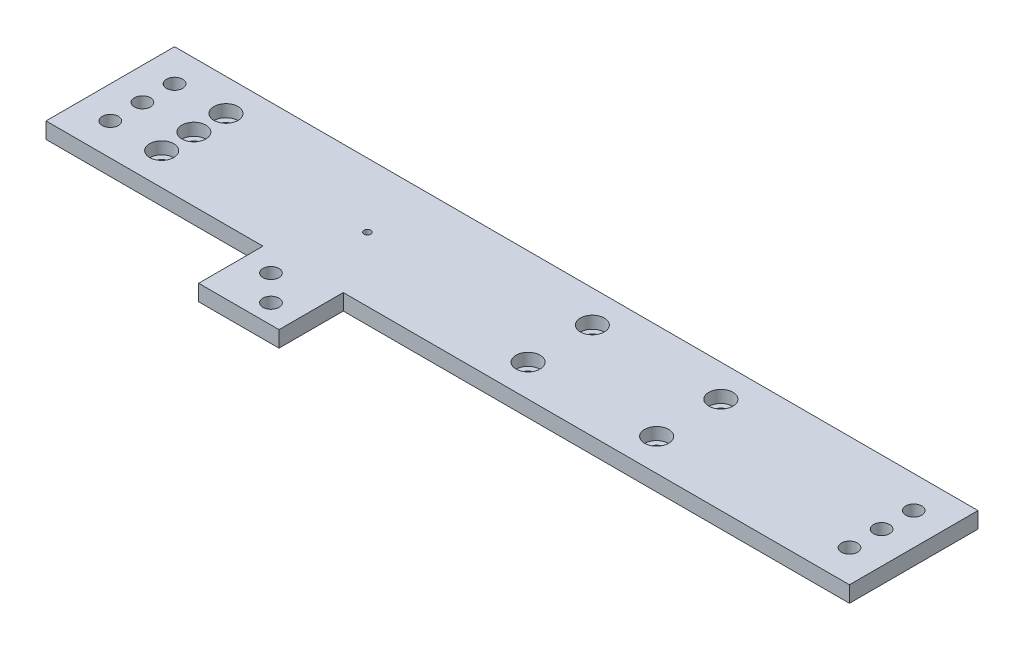
SolidWorks part; units mm, degrees
material "6061-T6 (SS)"
ref_plane "Front" through (0, 0, 0) normal (0, 0, 1) x (1, 0, 0)
ref_plane "Top" through (0, 0, 0) normal (0, 1, 0) x (1, 0, 0)
ref_plane "Right" through (0, 0, 0) normal (1, 0, 0) x (0, 0, -1)
sketch "Sketch1" plane through (0, 0, 0) normal (0, 1, 0) x (1, 0, 0)
  line L1 (-158.75, -25.4) -> (158.75, -25.4)
  line L2 (-158.75, -25.4) -> (-158.75, 25.4)
  line L3 (-158.75, 25.4) -> (158.75, 25.4)
  line L4 (158.75, -25.4) -> (158.75, 25.4)
  line L5 (-158.75, -25.4) -> (158.75, 25.4) construction
  line L6 (-158.75, 25.4) -> (158.75, -25.4) construction
  point P0 (0, 0)
  dimension "D1" = 50.8
  dimension "D2" = 317.5
extrude "Boss-Extrude1" add sketch "Sketch1" along normal blind 6.35
hole_wizard "CBORE for #10 Socket Head Cap Screw1" positions "Sketch2" profile "Sketch4" counterbore size "#10" standard "ANSI Inch" end condition through all
sketch "Sketch2" plane through (0, 6.35, 0) normal (0, 1, 0) x (1, 0, 0)
  line L2 (158.75, 25.4) -> (-158.75, 25.4) construction
  line L6 (-158.75, -25.4) -> (158.75, -25.4) construction
  line L8 (-158.75, 25.4) -> (-158.75, -25.4) construction
  line L12 (158.75, -25.4) -> (158.75, 25.4) construction
  line L15 (19.05, 12.7) -> (19.05, 25.4) construction
  line L17 (19.05, -12.7) -> (19.05, -25.4) construction
  line L18 (-125.73, -25.4) -> (-125.73, -12.7) construction
  line L20 (-125.73, 0) -> (-125.73, 12.7) construction
  line L21 (-125.73, 12.7) -> (-125.73, 25.4) construction
  line L22 (-125.73, 0) -> (-125.73, -12.7) construction
  point P64 (19.05, 12.7)
  point P66 (69.85, 12.7)
  point P68 (19.05, -12.7)
  point P70 (69.85, -12.7)
  point P92 (-125.73, 12.7)
  point P94 (-125.73, 0)
  point P102 (-125.73, -12.7)
  dimension "D2" = 50.8
  dimension "D3" = 25.4
  dimension "D4" = 88.9
  dimension "D5" = 33.02
sketch "Sketch4" plane through (-125.73, 6.35, 12.7) normal (1, 0, 0) x (0, 0, 1)
  line L0 (0, 0) -> (0, 6.35)
  line L1 (0, 6.35) -> (2.5527, 6.35)
  line L3 (2.5527, 6.35) -> (2.5527, 4.826)
  line L4 (2.5527, 4.826) -> (4.7625, 4.826)
  line L5 (4.7625, 4.826) -> (4.7625, 0)
  line L7 (4.7625, 0) -> (0, 0)
  line L11 (0, -6.35) -> (0, 107.95) construction
  dimension "Thru Hole Dia." = 5.1054
  dimension "Thru Hole Depth" = 6.35
  dimension "C'Bore Dia." = 9.525
  dimension "C'Bore Depth" = 4.826
sketch "Sketch7" plane through (0, 0, 0) normal (0, -1, 0) x (1, 0, 0)
  line L0 (-146.05, 25.4) -> (-146.05, 12.7) construction
  line L1 (-158.75, 25.4) -> (158.75, 25.4) construction
  line L2 (-146.05, 12.7) -> (-146.05, 0) construction
  line L3 (-146.05, 0) -> (-146.05, -12.7) construction
  line L4 (-146.05, -12.7) -> (-146.05, -25.4) construction
  line L5 (158.75, -25.4) -> (-158.75, -25.4) construction
  line L7 (-158.75, -25.4) -> (-158.75, 25.4) construction
  line L8 (146.05, 25.4) -> (146.05, 12.7) construction
  line L9 (146.05, 12.7) -> (146.05, 0) construction
  line L10 (146.05, 0) -> (146.05, -12.7) construction
  line L11 (146.05, -12.7) -> (146.05, -25.4) construction
  line L13 (158.75, 25.4) -> (158.75, -25.4) construction
  point P0 (-146.05, 12.7)
  point P2 (-146.05, 0)
  point P4 (-146.05, -12.7)
  point P6 (146.05, 12.7)
  point P8 (146.05, 0)
  point P10 (146.05, -12.7)
  dimension "D1" = 12.7
  dimension "D2" = 12.7
hole_wizard "1/4 (0.25) Diameter Hole1" positions "Sketch7" profile "Sketch6" hole size "1/4" standard "ANSI Inch" end condition through all
sketch "Sketch6" plane through (-146.05, 0, 12.7) normal (1, 0, 0) x (0, 0, -1)
  line L0 (0, 0) -> (0, 6.35)
  line L1 (0, 6.35) -> (3.175, 6.35)
  line L2 (3.175, 6.35) -> (3.175, 0)
  line L5 (3.175, 0) -> (0, 0)
  line L11 (0, -6.35) -> (0, 107.95) construction
  dimension "Thru Hole Dia." = 6.35
  dimension "Thru Hole Depth" = 6.35
sketch "Sketch10" plane through (0, 0, 0) normal (0, -1, 0) x (-1, 0, 0)
  line L0 (158.75, 25.4) -> (158.75, -25.4) construction
  point P0 (57.15, 0)
  dimension "D1" = 101.6
hole_wizard "#6-32 Tapped Hole1" positions "Sketch10" profile "Sketch9" tap size "#6-32" standard "ANSI Inch" end condition through all
sketch "Sketch9" plane through (-57.15, 0, 0) normal (1, 0, 0) x (0, 0, -1)
  line L0 (0, 0) -> (0, 6.35)
  line L1 (0, 6.35) -> (1.3525, 6.35)
  line L2 (1.3525, 6.35) -> (1.3525, 0)
  line L5 (1.3525, 0) -> (0, 0)
  line L11 (0, -6.35) -> (0, 107.95) construction
  dimension "Thru Tap Drill Dia." = 2.7051
  dimension "Thru Tap Drill Depth" = 6.35
cosmetic thread "Hole Thread1" parameters "D2"=3.5052
sketch "Sketch11" plane through (0, 0, 0) normal (0, -1, 0) x (1, 0, 0)
  line L0 (158.75, -25.4) -> (-158.75, -25.4) construction
  line L1 (-70.0118, -25.4) -> (-48.1024, -25.4)
  line L2 (-70.0118, -25.4) -> (-70.0118, -45.81)
  line L3 (-70.0118, -45.81) -> (-48.1024, -45.81)
  line L4 (-48.1024, -25.4) -> (-48.1024, -45.81)
extrude "Boss-Extrude2" [suppressed] add sketch "Sketch11" against normal up to surface (6.35 mm away) up to face at (-57.15, 6.35, -1.3526)
sketch "Sketch12" plane through (0, 6.35, 0) normal (0, 1, 0) x (1, 0, 0)
  line L0 (-158.75, -25.4) -> (158.75, -25.4) construction
  line L1 (-73.025, -25.4) -> (-41.275, -25.4)
  line L2 (-73.025, -25.4) -> (-73.025, -50.8)
  line L3 (-73.025, -50.8) -> (-41.275, -50.8)
  line L4 (-41.275, -25.4) -> (-41.275, -50.8)
  line L5 (-158.75, 25.4) -> (-158.75, -25.4) construction
  dimension "D1" = 85.725
  dimension "D2" = 31.75
  dimension "D3" = 25.4
extrude "Boss-Extrude3" add sketch "Sketch12" against normal up to surface (6.35 mm away) up to face at (-57.15, 0, -1.3526)
sketch "Sketch15" plane through (0, 0, 0) normal (0, -1, 0) x (-1, 0, 0)
  point P0 (52.07, -43.18)
  point P3 (62.23, -33.02)
hole_wizard "1/4 (0.25) Diameter Hole2" positions "Sketch15" profile "Sketch14" hole size "1/4" standard "ANSI Inch" end condition through all
sketch "Sketch14" plane through (-52.07, 0, 43.18) normal (1, 0, 0) x (0, 0, -1)
  line L0 (0, 0) -> (0, 6.35)
  line L1 (0, 6.35) -> (3.175, 6.35)
  line L2 (3.175, 6.35) -> (3.175, 0)
  line L5 (3.175, 0) -> (0, 0)
  line L11 (0, -6.35) -> (0, 107.95) construction
  dimension "Thru Hole Dia." = 6.35
  dimension "Thru Hole Depth" = 6.35
